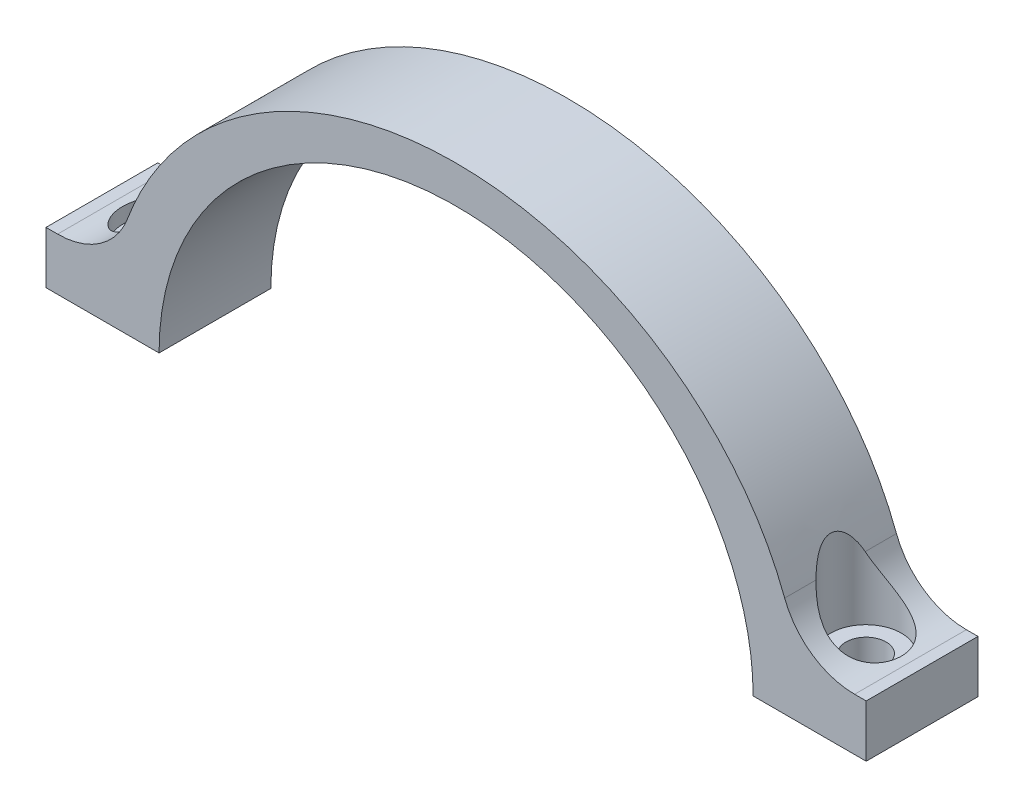
SolidWorks part; units mm, degrees
ref_plane "Front Plane" through (0, 0, 0) normal (0, 0, 1) x (1, 0, 0)
ref_plane "Top Plane" through (0, 0, 0) normal (0, 1, 0) x (1, 0, 0)
ref_plane "Right Plane" through (0, 0, 0) normal (1, 0, 0) x (0, 0, -1)
sketch "Sketch1" plane through (0, 0, 0) normal (0, 0, 1) x (1, 0, 0)
  line L0 (-39.855, 0) -> (-55.0244, 0)
  line L1 (39.855, 0) -> (55.0244, 0)
  line L2 (-55.0244, 0) -> (-55.0244, 7.0113)
  line L3 (55.0244, 0) -> (55.0244, 7.0113)
  line L4 (-55.0244, 7.0113) -> (-45.9009, 6.9897)
  line L5 (45.9009, 6.9897) -> (55.0244, 7.0113)
  ellipse E0 centre (0, 0) end of major axis (39.855, 0) minor radius 37 (-39.855, 0) -> (39.855, 0) cw
  ellipse E1 centre (0, 0) end of major axis (-46.5501, 0) minor radius 42 (-45.9009, 6.9897) -> (45.9009, 6.9897) cw
  dimension "D1" = 79.71
  dimension "D2" = 37
  dimension "D3" = 5
extrude "Boss-Extrude1" add sketch "Sketch1" along normal blind 15
fillet "Fillet1" radius 10 2 edges at (45.9009, 6.9897, 7.5) (-45.9009, 6.9897, 7.5)
sketch "Sketch3" plane through (0, 0, 0) normal (0, 1, 0) x (1, 0, 0)
  line L0 (0, 0) -> (0, -44.399) construction
  circle A0 centre (47.5, -7.5) radius 2.7
  circle A1 centre (-47.5, -7.5) radius 2.7
  point P4 (0, 0)
  point P5 (0, 0)
  dimension "D1" = 5.4
  dimension "D2" = 95
extrude "Cut-Extrude1" cut sketch "Sketch3" along normal blind 17 contours A1
extrude "Cut-Extrude2" cut sketch "Sketch3<4>" along normal blind 12 and the other way blind 1
sketch "Sketch3<4>" plane through (0, 0, 0) normal (0, 1, 0) x (1, 0, 0) same geometry as "Sketch3"
ref_plane "Plane1" through (0, 5, 0) normal (0, 1, 0) x (1, 0, 0)
sketch "Sketch5" plane through (0, 5, 0) normal (0, 1, 0) x (1, 0, 0)
  circle A0 centre (-47.5, -7.5) radius 4.75
  circle A1 centre (47.5, -7.5) radius 4.75
  dimension "D1" = 9.5
  dimension "D2" = 9.5
extrude "Cut-Extrude3" cut sketch "Sketch5" along normal blind 17
